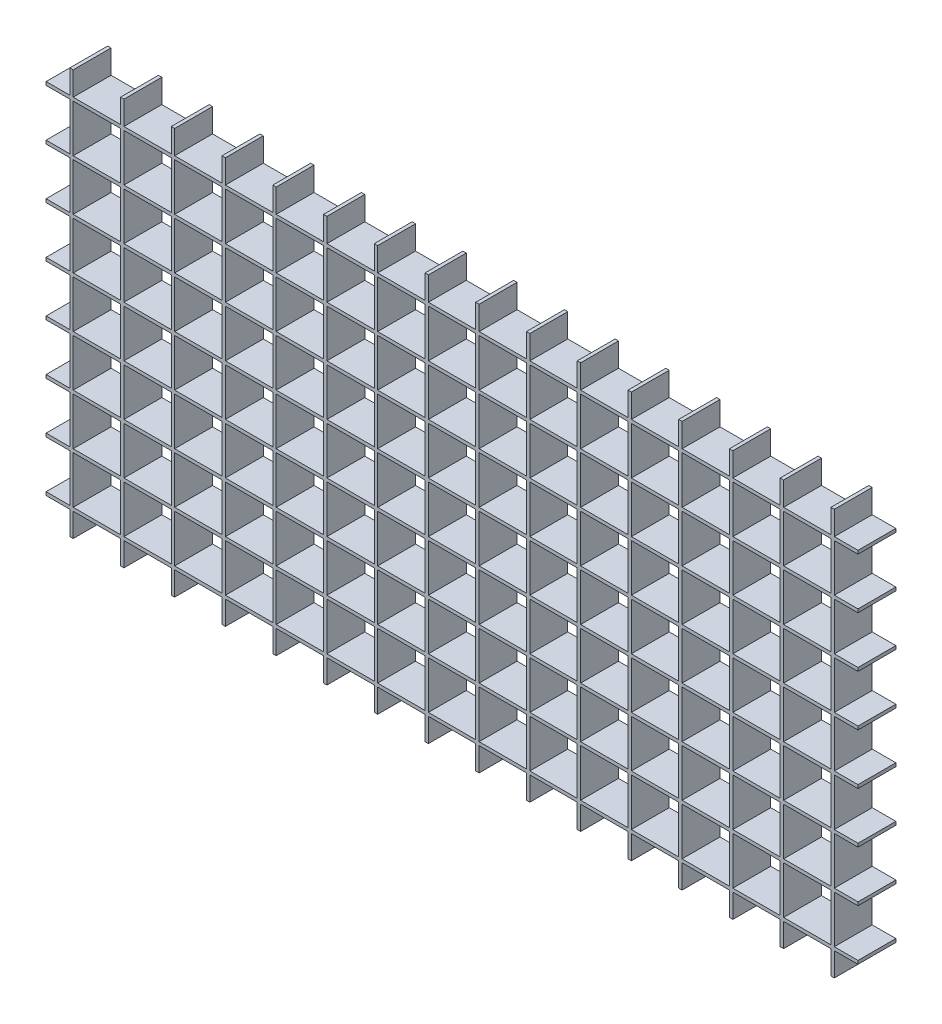
SolidWorks part; units mm, degrees
material "ABS"
ref_plane "Front Plane" through (0, 0, 0) normal (0, 0, 1) x (1, 0, 0)
ref_plane "Top Plane" through (0, 0, 0) normal (0, 1, 0) x (1, 0, 0)
ref_plane "Right Plane" through (0, 0, 0) normal (1, 0, 0) x (0, 0, -1)
sketch "Sketch1" plane through (0, 0, 0) normal (0, 0, 1) x (1, 0, 0)
  line L1 (0, 169.5652) -> (-600, 169.5652)
  line L2 (0, 169.5652) -> (0, -130.4348)
  line L3 (0, -130.4348) -> (-600, -130.4348)
  line L4 (-600, 169.5652) -> (-600, -130.4348)
  dimension "D1" = 600
  dimension "D2" = 300
extrude "Boss-Extrude1" add sketch "Sketch1" along normal blind 28
sketch "Sketch2" plane through (0, 0, 28) normal (0, 0, 1) x (1, 0, 0)
  line L0 (-20, 152.0652) -> (-55, 152.0652)
  line L1 (17.5, 187.0652) -> (-17.5, 187.0652)
  line L2 (17.5, 187.0652) -> (17.5, 152.0652)
  line L3 (17.5, 152.0652) -> (-17.5, 152.0652)
  line L4 (-17.5, 187.0652) -> (-17.5, 152.0652)
  line L5 (-20, 187.0652) -> (-20, 152.0652)
  line L6 (-20, 187.0652) -> (-55, 187.0652)
  line L7 (-55, 187.0652) -> (-55, 152.0652)
  line L8 (-57.5, 152.0652) -> (-92.5, 152.0652)
  line L9 (-57.5, 187.0652) -> (-57.5, 152.0652)
  line L10 (-57.5, 187.0652) -> (-92.5, 187.0652)
  line L11 (-92.5, 187.0652) -> (-92.5, 152.0652)
  line L12 (-95, 152.0652) -> (-130, 152.0652)
  line L13 (-95, 187.0652) -> (-95, 152.0652)
  line L14 (-95, 187.0652) -> (-130, 187.0652)
  line L15 (-130, 187.0652) -> (-130, 152.0652)
  line L16 (-132.5, 152.0652) -> (-167.5, 152.0652)
  line L17 (-132.5, 187.0652) -> (-132.5, 152.0652)
  line L18 (-132.5, 187.0652) -> (-167.5, 187.0652)
  line L19 (-167.5, 187.0652) -> (-167.5, 152.0652)
  line L20 (-170, 152.0652) -> (-205, 152.0652)
  line L21 (-170, 187.0652) -> (-170, 152.0652)
  line L22 (-170, 187.0652) -> (-205, 187.0652)
  line L23 (-205, 187.0652) -> (-205, 152.0652)
  line L24 (-207.5, 152.0652) -> (-242.5, 152.0652)
  line L25 (-207.5, 187.0652) -> (-207.5, 152.0652)
  line L26 (-207.5, 187.0652) -> (-242.5, 187.0652)
  line L27 (-242.5, 187.0652) -> (-242.5, 152.0652)
  line L28 (-245, 152.0652) -> (-280, 152.0652)
  line L29 (-245, 187.0652) -> (-245, 152.0652)
  line L30 (-245, 187.0652) -> (-280, 187.0652)
  line L31 (-280, 187.0652) -> (-280, 152.0652)
  line L32 (-282.5, 152.0652) -> (-317.5, 152.0652)
  line L33 (-282.5, 187.0652) -> (-282.5, 152.0652)
  line L34 (-282.5, 187.0652) -> (-317.5, 187.0652)
  line L35 (-317.5, 187.0652) -> (-317.5, 152.0652)
  line L36 (-320, 152.0652) -> (-355, 152.0652)
  line L37 (-320, 187.0652) -> (-320, 152.0652)
  line L38 (-320, 187.0652) -> (-355, 187.0652)
  line L39 (-355, 187.0652) -> (-355, 152.0652)
  line L40 (-357.5, 152.0652) -> (-392.5, 152.0652)
  line L41 (-357.5, 187.0652) -> (-357.5, 152.0652)
  line L42 (-357.5, 187.0652) -> (-392.5, 187.0652)
  line L43 (-392.5, 187.0652) -> (-392.5, 152.0652)
  line L44 (-395, 152.0652) -> (-430, 152.0652)
  line L45 (-395, 187.0652) -> (-395, 152.0652)
  line L46 (-395, 187.0652) -> (-430, 187.0652)
  line L47 (-430, 187.0652) -> (-430, 152.0652)
  line L48 (-432.5, 152.0652) -> (-467.5, 152.0652)
  line L49 (-432.5, 187.0652) -> (-432.5, 152.0652)
  line L50 (-432.5, 187.0652) -> (-467.5, 187.0652)
  line L51 (-467.5, 187.0652) -> (-467.5, 152.0652)
  line L52 (-470, 152.0652) -> (-505, 152.0652)
  line L53 (-470, 187.0652) -> (-470, 152.0652)
  line L54 (-470, 187.0652) -> (-505, 187.0652)
  line L55 (-505, 187.0652) -> (-505, 152.0652)
  line L56 (-507.5, 152.0652) -> (-542.5, 152.0652)
  line L57 (-507.5, 187.0652) -> (-507.5, 152.0652)
  line L58 (-507.5, 187.0652) -> (-542.5, 187.0652)
  line L59 (-542.5, 187.0652) -> (-542.5, 152.0652)
  line L60 (-545, 152.0652) -> (-580, 152.0652)
  line L61 (-545, 187.0652) -> (-545, 152.0652)
  line L62 (-545, 187.0652) -> (-580, 187.0652)
  line L63 (-580, 187.0652) -> (-580, 152.0652)
  line L64 (-582.5, 152.0652) -> (-617.5, 152.0652)
  line L65 (-582.5, 187.0652) -> (-582.5, 152.0652)
  line L66 (-582.5, 187.0652) -> (-617.5, 187.0652)
  line L67 (-617.5, 187.0652) -> (-617.5, 152.0652)
  line L68 (-20, 114.5652) -> (-55, 114.5652)
  line L69 (-20, 149.5652) -> (-20, 114.5652)
  line L70 (-20, 149.5652) -> (-55, 149.5652)
  line L71 (-55, 149.5652) -> (-55, 114.5652)
  line L72 (-57.5, 114.5652) -> (-92.5, 114.5652)
  line L73 (-57.5, 149.5652) -> (-57.5, 114.5652)
  line L74 (-57.5, 149.5652) -> (-92.5, 149.5652)
  line L75 (-92.5, 149.5652) -> (-92.5, 114.5652)
  line L76 (-95, 114.5652) -> (-130, 114.5652)
  line L77 (-95, 149.5652) -> (-95, 114.5652)
  line L78 (-95, 149.5652) -> (-130, 149.5652)
  line L79 (-130, 149.5652) -> (-130, 114.5652)
  line L80 (-132.5, 114.5652) -> (-167.5, 114.5652)
  line L81 (-132.5, 149.5652) -> (-132.5, 114.5652)
  line L82 (-132.5, 149.5652) -> (-167.5, 149.5652)
  line L83 (-167.5, 149.5652) -> (-167.5, 114.5652)
  line L84 (-170, 114.5652) -> (-205, 114.5652)
  line L85 (-170, 149.5652) -> (-170, 114.5652)
  line L86 (-170, 149.5652) -> (-205, 149.5652)
  line L87 (-205, 149.5652) -> (-205, 114.5652)
  line L88 (-207.5, 114.5652) -> (-242.5, 114.5652)
  line L89 (-207.5, 149.5652) -> (-207.5, 114.5652)
  line L90 (-207.5, 149.5652) -> (-242.5, 149.5652)
  line L91 (-242.5, 149.5652) -> (-242.5, 114.5652)
  line L92 (-245, 114.5652) -> (-280, 114.5652)
  line L93 (-245, 149.5652) -> (-245, 114.5652)
  line L94 (-245, 149.5652) -> (-280, 149.5652)
  line L95 (-280, 149.5652) -> (-280, 114.5652)
  line L96 (-282.5, 114.5652) -> (-317.5, 114.5652)
  line L97 (-282.5, 149.5652) -> (-282.5, 114.5652)
  line L98 (-282.5, 149.5652) -> (-317.5, 149.5652)
  line L99 (-317.5, 149.5652) -> (-317.5, 114.5652)
  line L100 (-320, 114.5652) -> (-355, 114.5652)
  line L101 (-320, 149.5652) -> (-320, 114.5652)
  line L102 (-320, 149.5652) -> (-355, 149.5652)
  line L103 (-355, 149.5652) -> (-355, 114.5652)
  line L104 (-357.5, 114.5652) -> (-392.5, 114.5652)
  line L105 (-357.5, 149.5652) -> (-357.5, 114.5652)
  line L106 (-357.5, 149.5652) -> (-392.5, 149.5652)
  line L107 (-392.5, 149.5652) -> (-392.5, 114.5652)
  line L108 (-395, 114.5652) -> (-430, 114.5652)
  line L109 (-395, 149.5652) -> (-395, 114.5652)
  line L110 (-395, 149.5652) -> (-430, 149.5652)
  line L111 (-430, 149.5652) -> (-430, 114.5652)
  line L112 (-432.5, 114.5652) -> (-467.5, 114.5652)
  line L113 (-432.5, 149.5652) -> (-432.5, 114.5652)
  line L114 (-432.5, 149.5652) -> (-467.5, 149.5652)
  line L115 (-467.5, 149.5652) -> (-467.5, 114.5652)
  line L116 (-470, 114.5652) -> (-505, 114.5652)
  line L117 (-470, 149.5652) -> (-470, 114.5652)
  line L118 (-470, 149.5652) -> (-505, 149.5652)
  line L119 (-505, 149.5652) -> (-505, 114.5652)
  line L120 (-507.5, 114.5652) -> (-542.5, 114.5652)
  line L121 (-507.5, 149.5652) -> (-507.5, 114.5652)
  line L122 (-507.5, 149.5652) -> (-542.5, 149.5652)
  line L123 (-542.5, 149.5652) -> (-542.5, 114.5652)
  line L124 (-545, 114.5652) -> (-580, 114.5652)
  line L125 (-545, 149.5652) -> (-545, 114.5652)
  line L126 (-545, 149.5652) -> (-580, 149.5652)
  line L127 (-580, 149.5652) -> (-580, 114.5652)
  line L128 (-582.5, 114.5652) -> (-617.5, 114.5652)
  line L129 (-582.5, 149.5652) -> (-582.5, 114.5652)
  line L130 (-582.5, 149.5652) -> (-617.5, 149.5652)
  line L131 (-617.5, 149.5652) -> (-617.5, 114.5652)
  line L132 (-20, 77.0652) -> (-55, 77.0652)
  line L133 (-20, 112.0652) -> (-20, 77.0652)
  line L134 (-20, 112.0652) -> (-55, 112.0652)
  line L135 (-55, 112.0652) -> (-55, 77.0652)
  line L136 (-57.5, 77.0652) -> (-92.5, 77.0652)
  line L137 (-57.5, 112.0652) -> (-57.5, 77.0652)
  line L138 (-57.5, 112.0652) -> (-92.5, 112.0652)
  line L139 (-92.5, 112.0652) -> (-92.5, 77.0652)
  line L140 (-95, 77.0652) -> (-130, 77.0652)
  line L141 (-95, 112.0652) -> (-95, 77.0652)
  line L142 (-95, 112.0652) -> (-130, 112.0652)
  line L143 (-130, 112.0652) -> (-130, 77.0652)
  line L144 (-132.5, 77.0652) -> (-167.5, 77.0652)
  line L145 (-132.5, 112.0652) -> (-132.5, 77.0652)
  line L146 (-132.5, 112.0652) -> (-167.5, 112.0652)
  line L147 (-167.5, 112.0652) -> (-167.5, 77.0652)
  line L148 (-170, 77.0652) -> (-205, 77.0652)
  line L149 (-170, 112.0652) -> (-170, 77.0652)
  line L150 (-170, 112.0652) -> (-205, 112.0652)
  line L151 (-205, 112.0652) -> (-205, 77.0652)
  line L152 (-207.5, 77.0652) -> (-242.5, 77.0652)
  line L153 (-207.5, 112.0652) -> (-207.5, 77.0652)
  line L154 (-207.5, 112.0652) -> (-242.5, 112.0652)
  line L155 (-242.5, 112.0652) -> (-242.5, 77.0652)
  line L156 (-245, 77.0652) -> (-280, 77.0652)
  line L157 (-245, 112.0652) -> (-245, 77.0652)
  line L158 (-245, 112.0652) -> (-280, 112.0652)
  line L159 (-280, 112.0652) -> (-280, 77.0652)
  line L160 (-282.5, 77.0652) -> (-317.5, 77.0652)
  line L161 (-282.5, 112.0652) -> (-282.5, 77.0652)
  line L162 (-282.5, 112.0652) -> (-317.5, 112.0652)
  line L163 (-317.5, 112.0652) -> (-317.5, 77.0652)
  line L164 (-320, 77.0652) -> (-355, 77.0652)
  line L165 (-320, 112.0652) -> (-320, 77.0652)
  line L166 (-320, 112.0652) -> (-355, 112.0652)
  line L167 (-355, 112.0652) -> (-355, 77.0652)
  line L168 (-357.5, 77.0652) -> (-392.5, 77.0652)
  line L169 (-357.5, 112.0652) -> (-357.5, 77.0652)
  line L170 (-357.5, 112.0652) -> (-392.5, 112.0652)
  line L171 (-392.5, 112.0652) -> (-392.5, 77.0652)
  line L172 (-395, 77.0652) -> (-430, 77.0652)
  line L173 (-395, 112.0652) -> (-395, 77.0652)
  line L174 (-395, 112.0652) -> (-430, 112.0652)
  line L175 (-430, 112.0652) -> (-430, 77.0652)
  line L176 (-432.5, 77.0652) -> (-467.5, 77.0652)
  line L177 (-432.5, 112.0652) -> (-432.5, 77.0652)
  line L178 (-432.5, 112.0652) -> (-467.5, 112.0652)
  line L179 (-467.5, 112.0652) -> (-467.5, 77.0652)
  line L180 (-470, 77.0652) -> (-505, 77.0652)
  line L181 (-470, 112.0652) -> (-470, 77.0652)
  line L182 (-470, 112.0652) -> (-505, 112.0652)
  line L183 (-505, 112.0652) -> (-505, 77.0652)
  line L184 (-507.5, 77.0652) -> (-542.5, 77.0652)
  line L185 (-507.5, 112.0652) -> (-507.5, 77.0652)
  line L186 (-507.5, 112.0652) -> (-542.5, 112.0652)
  line L187 (-542.5, 112.0652) -> (-542.5, 77.0652)
  line L188 (-545, 77.0652) -> (-580, 77.0652)
  line L189 (-545, 112.0652) -> (-545, 77.0652)
  line L190 (-545, 112.0652) -> (-580, 112.0652)
  line L191 (-580, 112.0652) -> (-580, 77.0652)
  line L192 (-582.5, 77.0652) -> (-617.5, 77.0652)
  line L193 (-582.5, 112.0652) -> (-582.5, 77.0652)
  line L194 (-582.5, 112.0652) -> (-617.5, 112.0652)
  line L195 (-617.5, 112.0652) -> (-617.5, 77.0652)
  line L196 (-20, 39.5652) -> (-55, 39.5652)
  line L197 (-20, 74.5652) -> (-20, 39.5652)
  line L198 (-20, 74.5652) -> (-55, 74.5652)
  line L199 (-55, 74.5652) -> (-55, 39.5652)
  line L200 (-57.5, 39.5652) -> (-92.5, 39.5652)
  line L201 (-57.5, 74.5652) -> (-57.5, 39.5652)
  line L202 (-57.5, 74.5652) -> (-92.5, 74.5652)
  line L203 (-92.5, 74.5652) -> (-92.5, 39.5652)
  line L204 (-95, 39.5652) -> (-130, 39.5652)
  line L205 (-95, 74.5652) -> (-95, 39.5652)
  line L206 (-95, 74.5652) -> (-130, 74.5652)
  line L207 (-130, 74.5652) -> (-130, 39.5652)
  line L208 (-132.5, 39.5652) -> (-167.5, 39.5652)
  line L209 (-132.5, 74.5652) -> (-132.5, 39.5652)
  line L210 (-132.5, 74.5652) -> (-167.5, 74.5652)
  line L211 (-167.5, 74.5652) -> (-167.5, 39.5652)
  line L212 (-170, 39.5652) -> (-205, 39.5652)
  line L213 (-170, 74.5652) -> (-170, 39.5652)
  line L214 (-170, 74.5652) -> (-205, 74.5652)
  line L215 (-205, 74.5652) -> (-205, 39.5652)
  line L216 (-207.5, 39.5652) -> (-242.5, 39.5652)
  line L217 (-207.5, 74.5652) -> (-207.5, 39.5652)
  line L218 (-207.5, 74.5652) -> (-242.5, 74.5652)
  line L219 (-242.5, 74.5652) -> (-242.5, 39.5652)
  line L220 (-245, 39.5652) -> (-280, 39.5652)
  line L221 (-245, 74.5652) -> (-245, 39.5652)
  line L222 (-245, 74.5652) -> (-280, 74.5652)
  line L223 (-280, 74.5652) -> (-280, 39.5652)
  line L224 (-282.5, 39.5652) -> (-317.5, 39.5652)
  line L225 (-282.5, 74.5652) -> (-282.5, 39.5652)
  line L226 (-282.5, 74.5652) -> (-317.5, 74.5652)
  line L227 (-317.5, 74.5652) -> (-317.5, 39.5652)
  line L228 (-320, 39.5652) -> (-355, 39.5652)
  line L229 (-320, 74.5652) -> (-320, 39.5652)
  line L230 (-320, 74.5652) -> (-355, 74.5652)
  line L231 (-355, 74.5652) -> (-355, 39.5652)
  line L232 (-357.5, 39.5652) -> (-392.5, 39.5652)
  line L233 (-357.5, 74.5652) -> (-357.5, 39.5652)
  line L234 (-357.5, 74.5652) -> (-392.5, 74.5652)
  line L235 (-392.5, 74.5652) -> (-392.5, 39.5652)
  line L236 (-395, 39.5652) -> (-430, 39.5652)
  line L237 (-395, 74.5652) -> (-395, 39.5652)
  line L238 (-395, 74.5652) -> (-430, 74.5652)
  line L239 (-430, 74.5652) -> (-430, 39.5652)
  line L240 (-432.5, 39.5652) -> (-467.5, 39.5652)
  line L241 (-432.5, 74.5652) -> (-432.5, 39.5652)
  line L242 (-432.5, 74.5652) -> (-467.5, 74.5652)
  line L243 (-467.5, 74.5652) -> (-467.5, 39.5652)
  line L244 (-470, 39.5652) -> (-505, 39.5652)
  line L245 (-470, 74.5652) -> (-470, 39.5652)
  line L246 (-470, 74.5652) -> (-505, 74.5652)
  line L247 (-505, 74.5652) -> (-505, 39.5652)
  line L248 (-507.5, 39.5652) -> (-542.5, 39.5652)
  line L249 (-507.5, 74.5652) -> (-507.5, 39.5652)
  line L250 (-507.5, 74.5652) -> (-542.5, 74.5652)
  line L251 (-542.5, 74.5652) -> (-542.5, 39.5652)
  line L252 (-545, 39.5652) -> (-580, 39.5652)
  line L253 (-545, 74.5652) -> (-545, 39.5652)
  line L254 (-545, 74.5652) -> (-580, 74.5652)
  line L255 (-580, 74.5652) -> (-580, 39.5652)
  line L256 (-582.5, 39.5652) -> (-617.5, 39.5652)
  line L257 (-582.5, 74.5652) -> (-582.5, 39.5652)
  line L258 (-582.5, 74.5652) -> (-617.5, 74.5652)
  line L259 (-617.5, 74.5652) -> (-617.5, 39.5652)
  line L260 (-20, 2.0652) -> (-55, 2.0652)
  line L261 (-20, 37.0652) -> (-20, 2.0652)
  line L262 (-20, 37.0652) -> (-55, 37.0652)
  line L263 (-55, 37.0652) -> (-55, 2.0652)
  line L264 (-57.5, 2.0652) -> (-92.5, 2.0652)
  line L265 (-57.5, 37.0652) -> (-57.5, 2.0652)
  line L266 (-57.5, 37.0652) -> (-92.5, 37.0652)
  line L267 (-92.5, 37.0652) -> (-92.5, 2.0652)
  line L268 (-95, 2.0652) -> (-130, 2.0652)
  line L269 (-95, 37.0652) -> (-95, 2.0652)
  line L270 (-95, 37.0652) -> (-130, 37.0652)
  line L271 (-130, 37.0652) -> (-130, 2.0652)
  line L272 (-132.5, 2.0652) -> (-167.5, 2.0652)
  line L273 (-132.5, 37.0652) -> (-132.5, 2.0652)
  line L274 (-132.5, 37.0652) -> (-167.5, 37.0652)
  line L275 (-167.5, 37.0652) -> (-167.5, 2.0652)
  line L276 (-170, 2.0652) -> (-205, 2.0652)
  line L277 (-170, 37.0652) -> (-170, 2.0652)
  line L278 (-170, 37.0652) -> (-205, 37.0652)
  line L279 (-205, 37.0652) -> (-205, 2.0652)
  line L280 (-207.5, 2.0652) -> (-242.5, 2.0652)
  line L281 (-207.5, 37.0652) -> (-207.5, 2.0652)
  line L282 (-207.5, 37.0652) -> (-242.5, 37.0652)
  line L283 (-242.5, 37.0652) -> (-242.5, 2.0652)
  line L284 (-245, 2.0652) -> (-280, 2.0652)
  line L285 (-245, 37.0652) -> (-245, 2.0652)
  line L286 (-245, 37.0652) -> (-280, 37.0652)
  line L287 (-280, 37.0652) -> (-280, 2.0652)
  line L288 (-282.5, 2.0652) -> (-317.5, 2.0652)
  line L289 (-282.5, 37.0652) -> (-282.5, 2.0652)
  line L290 (-282.5, 37.0652) -> (-317.5, 37.0652)
  line L291 (-317.5, 37.0652) -> (-317.5, 2.0652)
  line L292 (-320, 2.0652) -> (-355, 2.0652)
  line L293 (-320, 37.0652) -> (-320, 2.0652)
  line L294 (-320, 37.0652) -> (-355, 37.0652)
  line L295 (-355, 37.0652) -> (-355, 2.0652)
  line L296 (-357.5, 2.0652) -> (-392.5, 2.0652)
  line L297 (-357.5, 37.0652) -> (-357.5, 2.0652)
  line L298 (-357.5, 37.0652) -> (-392.5, 37.0652)
  line L299 (-392.5, 37.0652) -> (-392.5, 2.0652)
  line L300 (-395, 2.0652) -> (-430, 2.0652)
  line L301 (-395, 37.0652) -> (-395, 2.0652)
  line L302 (-395, 37.0652) -> (-430, 37.0652)
  line L303 (-430, 37.0652) -> (-430, 2.0652)
  line L304 (-432.5, 2.0652) -> (-467.5, 2.0652)
  line L305 (-432.5, 37.0652) -> (-432.5, 2.0652)
  line L306 (-432.5, 37.0652) -> (-467.5, 37.0652)
  line L307 (-467.5, 37.0652) -> (-467.5, 2.0652)
  line L308 (-470, 2.0652) -> (-505, 2.0652)
  line L309 (-470, 37.0652) -> (-470, 2.0652)
  line L310 (-470, 37.0652) -> (-505, 37.0652)
  line L311 (-505, 37.0652) -> (-505, 2.0652)
  line L312 (-507.5, 2.0652) -> (-542.5, 2.0652)
  line L313 (-507.5, 37.0652) -> (-507.5, 2.0652)
  line L314 (-507.5, 37.0652) -> (-542.5, 37.0652)
  line L315 (-542.5, 37.0652) -> (-542.5, 2.0652)
  line L316 (-545, 2.0652) -> (-580, 2.0652)
  line L317 (-545, 37.0652) -> (-545, 2.0652)
  line L318 (-545, 37.0652) -> (-580, 37.0652)
  line L319 (-580, 37.0652) -> (-580, 2.0652)
  line L320 (-582.5, 2.0652) -> (-617.5, 2.0652)
  line L321 (-582.5, 37.0652) -> (-582.5, 2.0652)
  line L322 (-582.5, 37.0652) -> (-617.5, 37.0652)
  line L323 (-617.5, 37.0652) -> (-617.5, 2.0652)
  line L324 (-20, -35.4348) -> (-55, -35.4348)
  line L325 (-20, -0.4348) -> (-20, -35.4348)
  line L326 (-20, -0.4348) -> (-55, -0.4348)
  line L327 (-55, -0.4348) -> (-55, -35.4348)
  line L328 (-57.5, -35.4348) -> (-92.5, -35.4348)
  line L329 (-57.5, -0.4348) -> (-57.5, -35.4348)
  line L330 (-57.5, -0.4348) -> (-92.5, -0.4348)
  line L331 (-92.5, -0.4348) -> (-92.5, -35.4348)
  line L332 (-95, -35.4348) -> (-130, -35.4348)
  line L333 (-95, -0.4348) -> (-95, -35.4348)
  line L334 (-95, -0.4348) -> (-130, -0.4348)
  line L335 (-130, -0.4348) -> (-130, -35.4348)
  line L336 (-132.5, -35.4348) -> (-167.5, -35.4348)
  line L337 (-132.5, -0.4348) -> (-132.5, -35.4348)
  line L338 (-132.5, -0.4348) -> (-167.5, -0.4348)
  line L339 (-167.5, -0.4348) -> (-167.5, -35.4348)
  line L340 (-170, -35.4348) -> (-205, -35.4348)
  line L341 (-170, -0.4348) -> (-170, -35.4348)
  line L342 (-170, -0.4348) -> (-205, -0.4348)
  line L343 (-205, -0.4348) -> (-205, -35.4348)
  line L344 (-207.5, -35.4348) -> (-242.5, -35.4348)
  line L345 (-207.5, -0.4348) -> (-207.5, -35.4348)
  line L346 (-207.5, -0.4348) -> (-242.5, -0.4348)
  line L347 (-242.5, -0.4348) -> (-242.5, -35.4348)
  line L348 (-245, -35.4348) -> (-280, -35.4348)
  line L349 (-245, -0.4348) -> (-245, -35.4348)
  line L350 (-245, -0.4348) -> (-280, -0.4348)
  line L351 (-280, -0.4348) -> (-280, -35.4348)
  line L352 (-282.5, -35.4348) -> (-317.5, -35.4348)
  line L353 (-282.5, -0.4348) -> (-282.5, -35.4348)
  line L354 (-282.5, -0.4348) -> (-317.5, -0.4348)
  line L355 (-317.5, -0.4348) -> (-317.5, -35.4348)
  line L356 (-320, -35.4348) -> (-355, -35.4348)
  line L357 (-320, -0.4348) -> (-320, -35.4348)
  line L358 (-320, -0.4348) -> (-355, -0.4348)
  line L359 (-355, -0.4348) -> (-355, -35.4348)
  line L360 (-357.5, -35.4348) -> (-392.5, -35.4348)
  line L361 (-357.5, -0.4348) -> (-357.5, -35.4348)
  line L362 (-357.5, -0.4348) -> (-392.5, -0.4348)
  line L363 (-392.5, -0.4348) -> (-392.5, -35.4348)
  line L364 (-395, -35.4348) -> (-430, -35.4348)
  line L365 (-395, -0.4348) -> (-395, -35.4348)
  line L366 (-395, -0.4348) -> (-430, -0.4348)
  line L367 (-430, -0.4348) -> (-430, -35.4348)
  line L368 (-432.5, -35.4348) -> (-467.5, -35.4348)
  line L369 (-432.5, -0.4348) -> (-432.5, -35.4348)
  line L370 (-432.5, -0.4348) -> (-467.5, -0.4348)
  line L371 (-467.5, -0.4348) -> (-467.5, -35.4348)
  line L372 (-470, -35.4348) -> (-505, -35.4348)
  line L373 (-470, -0.4348) -> (-470, -35.4348)
  line L374 (-470, -0.4348) -> (-505, -0.4348)
  line L375 (-505, -0.4348) -> (-505, -35.4348)
  line L376 (-507.5, -35.4348) -> (-542.5, -35.4348)
  line L377 (-507.5, -0.4348) -> (-507.5, -35.4348)
  line L378 (-507.5, -0.4348) -> (-542.5, -0.4348)
  line L379 (-542.5, -0.4348) -> (-542.5, -35.4348)
  line L380 (-545, -35.4348) -> (-580, -35.4348)
  line L381 (-545, -0.4348) -> (-545, -35.4348)
  line L382 (-545, -0.4348) -> (-580, -0.4348)
  line L383 (-580, -0.4348) -> (-580, -35.4348)
  line L384 (-582.5, -35.4348) -> (-617.5, -35.4348)
  line L385 (-582.5, -0.4348) -> (-582.5, -35.4348)
  line L386 (-582.5, -0.4348) -> (-617.5, -0.4348)
  line L387 (-617.5, -0.4348) -> (-617.5, -35.4348)
  line L388 (-20, -72.9348) -> (-55, -72.9348)
  line L389 (-20, -37.9348) -> (-20, -72.9348)
  line L390 (-20, -37.9348) -> (-55, -37.9348)
  line L391 (-55, -37.9348) -> (-55, -72.9348)
  line L392 (-57.5, -72.9348) -> (-92.5, -72.9348)
  line L393 (-57.5, -37.9348) -> (-57.5, -72.9348)
  line L394 (-57.5, -37.9348) -> (-92.5, -37.9348)
  line L395 (-92.5, -37.9348) -> (-92.5, -72.9348)
  line L396 (-95, -72.9348) -> (-130, -72.9348)
  line L397 (-95, -37.9348) -> (-95, -72.9348)
  line L398 (-95, -37.9348) -> (-130, -37.9348)
  line L399 (-130, -37.9348) -> (-130, -72.9348)
  line L400 (-132.5, -72.9348) -> (-167.5, -72.9348)
  line L401 (-132.5, -37.9348) -> (-132.5, -72.9348)
  line L402 (-132.5, -37.9348) -> (-167.5, -37.9348)
  line L403 (-167.5, -37.9348) -> (-167.5, -72.9348)
  line L404 (-170, -72.9348) -> (-205, -72.9348)
  line L405 (-170, -37.9348) -> (-170, -72.9348)
  line L406 (-170, -37.9348) -> (-205, -37.9348)
  line L407 (-205, -37.9348) -> (-205, -72.9348)
  line L408 (-207.5, -72.9348) -> (-242.5, -72.9348)
  line L409 (-207.5, -37.9348) -> (-207.5, -72.9348)
  line L410 (-207.5, -37.9348) -> (-242.5, -37.9348)
  line L411 (-242.5, -37.9348) -> (-242.5, -72.9348)
  line L412 (-245, -72.9348) -> (-280, -72.9348)
  line L413 (-245, -37.9348) -> (-245, -72.9348)
  line L414 (-245, -37.9348) -> (-280, -37.9348)
  line L415 (-280, -37.9348) -> (-280, -72.9348)
  line L416 (-282.5, -72.9348) -> (-317.5, -72.9348)
  line L417 (-282.5, -37.9348) -> (-282.5, -72.9348)
  line L418 (-282.5, -37.9348) -> (-317.5, -37.9348)
  line L419 (-317.5, -37.9348) -> (-317.5, -72.9348)
  line L420 (-320, -72.9348) -> (-355, -72.9348)
  line L421 (-320, -37.9348) -> (-320, -72.9348)
  line L422 (-320, -37.9348) -> (-355, -37.9348)
  line L423 (-355, -37.9348) -> (-355, -72.9348)
  line L424 (-357.5, -72.9348) -> (-392.5, -72.9348)
  line L425 (-357.5, -37.9348) -> (-357.5, -72.9348)
  line L426 (-357.5, -37.9348) -> (-392.5, -37.9348)
  line L427 (-392.5, -37.9348) -> (-392.5, -72.9348)
  line L428 (-395, -72.9348) -> (-430, -72.9348)
  line L429 (-395, -37.9348) -> (-395, -72.9348)
  line L430 (-395, -37.9348) -> (-430, -37.9348)
  line L431 (-430, -37.9348) -> (-430, -72.9348)
  line L432 (-432.5, -72.9348) -> (-467.5, -72.9348)
  line L433 (-432.5, -37.9348) -> (-432.5, -72.9348)
  line L434 (-432.5, -37.9348) -> (-467.5, -37.9348)
  line L435 (-467.5, -37.9348) -> (-467.5, -72.9348)
  line L436 (-470, -72.9348) -> (-505, -72.9348)
  line L437 (-470, -37.9348) -> (-470, -72.9348)
  line L438 (-470, -37.9348) -> (-505, -37.9348)
  line L439 (-505, -37.9348) -> (-505, -72.9348)
  line L440 (-507.5, -72.9348) -> (-542.5, -72.9348)
  line L441 (-507.5, -37.9348) -> (-507.5, -72.9348)
  line L442 (-507.5, -37.9348) -> (-542.5, -37.9348)
  line L443 (-542.5, -37.9348) -> (-542.5, -72.9348)
  line L444 (-545, -72.9348) -> (-580, -72.9348)
  line L445 (-545, -37.9348) -> (-545, -72.9348)
  line L446 (-545, -37.9348) -> (-580, -37.9348)
  line L447 (-580, -37.9348) -> (-580, -72.9348)
  line L448 (-582.5, -72.9348) -> (-617.5, -72.9348)
  line L449 (-582.5, -37.9348) -> (-582.5, -72.9348)
  line L450 (-582.5, -37.9348) -> (-617.5, -37.9348)
  line L451 (-617.5, -37.9348) -> (-617.5, -72.9348)
  line L452 (-20, -110.4348) -> (-55, -110.4348)
  line L453 (-20, -75.4348) -> (-20, -110.4348)
  line L454 (-20, -75.4348) -> (-55, -75.4348)
  line L455 (-55, -75.4348) -> (-55, -110.4348)
  line L456 (-57.5, -110.4348) -> (-92.5, -110.4348)
  line L457 (-57.5, -75.4348) -> (-57.5, -110.4348)
  line L458 (-57.5, -75.4348) -> (-92.5, -75.4348)
  line L459 (-92.5, -75.4348) -> (-92.5, -110.4348)
  line L460 (-95, -110.4348) -> (-130, -110.4348)
  line L461 (-95, -75.4348) -> (-95, -110.4348)
  line L462 (-95, -75.4348) -> (-130, -75.4348)
  line L463 (-130, -75.4348) -> (-130, -110.4348)
  line L464 (-132.5, -110.4348) -> (-167.5, -110.4348)
  line L465 (-132.5, -75.4348) -> (-132.5, -110.4348)
  line L466 (-132.5, -75.4348) -> (-167.5, -75.4348)
  line L467 (-167.5, -75.4348) -> (-167.5, -110.4348)
  line L468 (-170, -110.4348) -> (-205, -110.4348)
  line L469 (-170, -75.4348) -> (-170, -110.4348)
  line L470 (-170, -75.4348) -> (-205, -75.4348)
  line L471 (-205, -75.4348) -> (-205, -110.4348)
  line L472 (-207.5, -110.4348) -> (-242.5, -110.4348)
  line L473 (-207.5, -75.4348) -> (-207.5, -110.4348)
  line L474 (-207.5, -75.4348) -> (-242.5, -75.4348)
  line L475 (-242.5, -75.4348) -> (-242.5, -110.4348)
  line L476 (-245, -110.4348) -> (-280, -110.4348)
  line L477 (-245, -75.4348) -> (-245, -110.4348)
  line L478 (-245, -75.4348) -> (-280, -75.4348)
  line L479 (-280, -75.4348) -> (-280, -110.4348)
  line L480 (-282.5, -110.4348) -> (-317.5, -110.4348)
  line L481 (-282.5, -75.4348) -> (-282.5, -110.4348)
  line L482 (-282.5, -75.4348) -> (-317.5, -75.4348)
  line L483 (-317.5, -75.4348) -> (-317.5, -110.4348)
  line L484 (-320, -110.4348) -> (-355, -110.4348)
  line L485 (-320, -75.4348) -> (-320, -110.4348)
  line L486 (-320, -75.4348) -> (-355, -75.4348)
  line L487 (-355, -75.4348) -> (-355, -110.4348)
  line L488 (-357.5, -110.4348) -> (-392.5, -110.4348)
  line L489 (-357.5, -75.4348) -> (-357.5, -110.4348)
  line L490 (-357.5, -75.4348) -> (-392.5, -75.4348)
  line L491 (-392.5, -75.4348) -> (-392.5, -110.4348)
  line L492 (-395, -110.4348) -> (-430, -110.4348)
  line L493 (-395, -75.4348) -> (-395, -110.4348)
  line L494 (-395, -75.4348) -> (-430, -75.4348)
  line L495 (-430, -75.4348) -> (-430, -110.4348)
  line L496 (-432.5, -110.4348) -> (-467.5, -110.4348)
  line L497 (-432.5, -75.4348) -> (-432.5, -110.4348)
  line L498 (-432.5, -75.4348) -> (-467.5, -75.4348)
  line L499 (-467.5, -75.4348) -> (-467.5, -110.4348)
  line L500 (-470, -110.4348) -> (-505, -110.4348)
  line L501 (-470, -75.4348) -> (-470, -110.4348)
  line L502 (-470, -75.4348) -> (-505, -75.4348)
  line L503 (-505, -75.4348) -> (-505, -110.4348)
  line L504 (-507.5, -110.4348) -> (-542.5, -110.4348)
  line L505 (-507.5, -75.4348) -> (-507.5, -110.4348)
  line L506 (-507.5, -75.4348) -> (-542.5, -75.4348)
  line L507 (-542.5, -75.4348) -> (-542.5, -110.4348)
  line L508 (-545, -110.4348) -> (-580, -110.4348)
  line L509 (-545, -75.4348) -> (-545, -110.4348)
  line L510 (-545, -75.4348) -> (-580, -75.4348)
  line L511 (-580, -75.4348) -> (-580, -110.4348)
  line L512 (-582.5, -110.4348) -> (-617.5, -110.4348)
  line L513 (-582.5, -75.4348) -> (-582.5, -110.4348)
  line L514 (-582.5, -75.4348) -> (-617.5, -75.4348)
  line L515 (-617.5, -75.4348) -> (-617.5, -110.4348)
  line L516 (-20, -147.9348) -> (-55, -147.9348)
  line L517 (-20, -112.9348) -> (-20, -147.9348)
  line L518 (-20, -112.9348) -> (-55, -112.9348)
  line L519 (-55, -112.9348) -> (-55, -147.9348)
  line L520 (-57.5, -147.9348) -> (-92.5, -147.9348)
  line L521 (-57.5, -112.9348) -> (-57.5, -147.9348)
  line L522 (-57.5, -112.9348) -> (-92.5, -112.9348)
  line L523 (-92.5, -112.9348) -> (-92.5, -147.9348)
  line L524 (-95, -147.9348) -> (-130, -147.9348)
  line L525 (-95, -112.9348) -> (-95, -147.9348)
  line L526 (-95, -112.9348) -> (-130, -112.9348)
  line L527 (-130, -112.9348) -> (-130, -147.9348)
  line L528 (-132.5, -147.9348) -> (-167.5, -147.9348)
  line L529 (-132.5, -112.9348) -> (-132.5, -147.9348)
  line L530 (-132.5, -112.9348) -> (-167.5, -112.9348)
  line L531 (-167.5, -112.9348) -> (-167.5, -147.9348)
  line L532 (-170, -147.9348) -> (-205, -147.9348)
  line L533 (-170, -112.9348) -> (-170, -147.9348)
  line L534 (-170, -112.9348) -> (-205, -112.9348)
  line L535 (-205, -112.9348) -> (-205, -147.9348)
  line L536 (-207.5, -147.9348) -> (-242.5, -147.9348)
  line L537 (-207.5, -112.9348) -> (-207.5, -147.9348)
  line L538 (-207.5, -112.9348) -> (-242.5, -112.9348)
  line L539 (-242.5, -112.9348) -> (-242.5, -147.9348)
  line L540 (-245, -147.9348) -> (-280, -147.9348)
  line L541 (-245, -112.9348) -> (-245, -147.9348)
  line L542 (-245, -112.9348) -> (-280, -112.9348)
  line L543 (-280, -112.9348) -> (-280, -147.9348)
  line L544 (-282.5, -147.9348) -> (-317.5, -147.9348)
  line L545 (-282.5, -112.9348) -> (-282.5, -147.9348)
  line L546 (-282.5, -112.9348) -> (-317.5, -112.9348)
  line L547 (-317.5, -112.9348) -> (-317.5, -147.9348)
  line L548 (-320, -147.9348) -> (-355, -147.9348)
  line L549 (-320, -112.9348) -> (-320, -147.9348)
  line L550 (-320, -112.9348) -> (-355, -112.9348)
  line L551 (-355, -112.9348) -> (-355, -147.9348)
  line L552 (-357.5, -147.9348) -> (-392.5, -147.9348)
  line L553 (-357.5, -112.9348) -> (-357.5, -147.9348)
  line L554 (-357.5, -112.9348) -> (-392.5, -112.9348)
  line L555 (-392.5, -112.9348) -> (-392.5, -147.9348)
  line L556 (-395, -147.9348) -> (-430, -147.9348)
  line L557 (-395, -112.9348) -> (-395, -147.9348)
  line L558 (-395, -112.9348) -> (-430, -112.9348)
  line L559 (-430, -112.9348) -> (-430, -147.9348)
  line L560 (-432.5, -147.9348) -> (-467.5, -147.9348)
  line L561 (-432.5, -112.9348) -> (-432.5, -147.9348)
  line L562 (-432.5, -112.9348) -> (-467.5, -112.9348)
  line L563 (-467.5, -112.9348) -> (-467.5, -147.9348)
  line L564 (-470, -147.9348) -> (-505, -147.9348)
  line L565 (-470, -112.9348) -> (-470, -147.9348)
  line L566 (-470, -112.9348) -> (-505, -112.9348)
  line L567 (-505, -112.9348) -> (-505, -147.9348)
  line L568 (-507.5, -147.9348) -> (-542.5, -147.9348)
  line L569 (-507.5, -112.9348) -> (-507.5, -147.9348)
  line L570 (-507.5, -112.9348) -> (-542.5, -112.9348)
  line L571 (-542.5, -112.9348) -> (-542.5, -147.9348)
  line L572 (-545, -147.9348) -> (-580, -147.9348)
  line L573 (-545, -112.9348) -> (-545, -147.9348)
  line L574 (-545, -112.9348) -> (-580, -112.9348)
  line L575 (-580, -112.9348) -> (-580, -147.9348)
  line L576 (-582.5, -147.9348) -> (-617.5, -147.9348)
  line L577 (-582.5, -112.9348) -> (-582.5, -147.9348)
  line L578 (-582.5, -112.9348) -> (-617.5, -112.9348)
  line L579 (-617.5, -112.9348) -> (-617.5, -147.9348)
  line L580 (17.5, 114.5652) -> (-17.5, 114.5652)
  line L581 (17.5, 149.5652) -> (17.5, 114.5652)
  line L582 (17.5, 149.5652) -> (-17.5, 149.5652)
  line L583 (-17.5, 149.5652) -> (-17.5, 114.5652)
  line L584 (17.5, 77.0652) -> (-17.5, 77.0652)
  line L585 (17.5, 112.0652) -> (17.5, 77.0652)
  line L586 (17.5, 112.0652) -> (-17.5, 112.0652)
  line L587 (-17.5, 112.0652) -> (-17.5, 77.0652)
  line L588 (17.5, 39.5652) -> (-17.5, 39.5652)
  line L589 (17.5, 74.5652) -> (17.5, 39.5652)
  line L590 (17.5, 74.5652) -> (-17.5, 74.5652)
  line L591 (-17.5, 74.5652) -> (-17.5, 39.5652)
  line L592 (17.5, 2.0652) -> (-17.5, 2.0652)
  line L593 (17.5, 37.0652) -> (17.5, 2.0652)
  line L594 (17.5, 37.0652) -> (-17.5, 37.0652)
  line L595 (-17.5, 37.0652) -> (-17.5, 2.0652)
  line L596 (17.5, -35.4348) -> (-17.5, -35.4348)
  line L597 (17.5, -0.4348) -> (17.5, -35.4348)
  line L598 (17.5, -0.4348) -> (-17.5, -0.4348)
  line L599 (-17.5, -0.4348) -> (-17.5, -35.4348)
  line L600 (17.5, -72.9348) -> (-17.5, -72.9348)
  line L601 (17.5, -37.9348) -> (17.5, -72.9348)
  line L602 (17.5, -37.9348) -> (-17.5, -37.9348)
  line L603 (-17.5, -37.9348) -> (-17.5, -72.9348)
  line L604 (17.5, -110.4348) -> (-17.5, -110.4348)
  line L605 (17.5, -75.4348) -> (17.5, -110.4348)
  line L606 (17.5, -75.4348) -> (-17.5, -75.4348)
  line L607 (-17.5, -75.4348) -> (-17.5, -110.4348)
  line L608 (17.5, -147.9348) -> (-17.5, -147.9348)
  line L609 (17.5, -112.9348) -> (17.5, -147.9348)
  line L610 (17.5, -112.9348) -> (-17.5, -112.9348)
  line L611 (-17.5, -112.9348) -> (-17.5, -147.9348)
  dimension "D1" = 35
  dimension "D2" = 35
  dimension "D3" = 17
  dimension "D4" = 9
extrude "Cut-Extrude1" cut sketch "Sketch2" against normal blind 28
